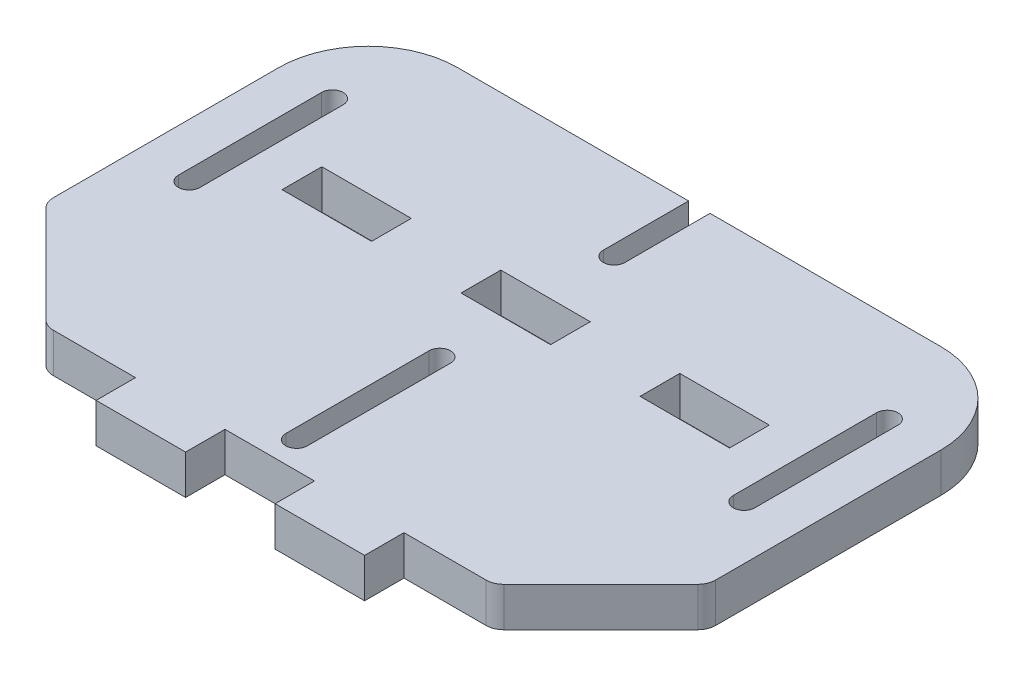
SolidWorks part; units mm, degrees
ref_plane "Front Plane" through (0, 0, 0) normal (0, 0, 1) x (1, 0, 0)
ref_plane "Top Plane" through (0, 0, 0) normal (0, 1, 0) x (1, 0, 0)
ref_plane "Right Plane" through (0, 0, 0) normal (1, 0, 0) x (0, 0, -1)
sketch "Sketch1" plane through (0, 0, 0) normal (0, 1, 0) x (1, 0, 0)
  line L8 (0, -7.5) -> (125, -7.5)
  line L12 (0, -7.5) -> (0, 3.5)
  line L14 (125, -7.5) -> (125, 3.5)
  line L17 (155, 33.5) -> (155, 123.5)
  line L18 (-30, 33.5) -> (-30, 123.5)
  line L23 (140, 58.5) -> (140, 98.5) construction
  line L24 (137, 58.5) -> (137, 98.5)
  line L25 (143, 58.5) -> (143, 98.5)
  line L26 (-15, 58.5) -> (-15, 98.5) construction
  line L27 (-18, 58.5) -> (-18, 98.5)
  line L28 (-12, 58.5) -> (-12, 98.5)
  line L29 (62.5, 11) -> (62.5, 51) construction
  line L30 (59.5, 11) -> (59.5, 51)
  line L31 (65.5, 11) -> (65.5, 51)
  line L32 (59.5, 123.5) -> (-30, 123.5)
  line L33 (65.5, 123.5) -> (65.5, 99.7057)
  line L34 (59.5, 123.5) -> (59.5, 99.7057)
  line L35 (155, 123.5) -> (65.5, 123.5)
  line L36 (125, 3.5) -> (155, 33.5)
  line L37 (0, 3.5) -> (-30, 33.5)
  arc A0 (137, 58.5) -> (143, 58.5) centre (140, 58.5) ccw
  arc A1 (143, 98.5) -> (137, 98.5) centre (140, 98.5) ccw
  arc A2 (-18, 58.5) -> (-12, 58.5) centre (-15, 58.5) ccw
  arc A3 (-12, 98.5) -> (-18, 98.5) centre (-15, 98.5) ccw
  arc A4 (59.5, 11) -> (65.5, 11) centre (62.5, 11) ccw
  arc A5 (65.5, 51) -> (59.5, 51) centre (62.5, 51) ccw
  arc A7 (59.5, 99.7057) -> (65.5, 99.7057) centre (62.5, 99.7057) ccw
  point P4 (-30, 78.5)
  point P18 (140, 78.5)
  point P23 (-15, 78.5)
  point P30 (62.5, 31)
  dimension "D7" = 15
  dimension "D8" = 45
  dimension "D9" = 3
  dimension "D10" = 40
  dimension "D13" = 15
  dimension "D1" = 89.5
  dimension "D12" = 3
  dimension "D2" = 135
  dimension "D3" = 11
  dimension "D4" = 135
  dimension "D5" = 125
  dimension "D6" = 90
extrude "Boss-Extrude6" add sketch "Sketch1" along normal blind 11
sketch "Sketch4" plane through (0, 11, 0) normal (0, 1, 0) x (1, 0, 0)
  line L0 (0, -7.5) -> (125, -7.5) construction
  line L1 (0, -7.5) -> (25, -7.5)
  line L2 (0, -7.5) -> (0, 3.5)
  line L3 (0, 3.5) -> (25, 3.5)
  line L4 (25, -7.5) -> (25, 3.5)
  line L5 (50, -7.5) -> (75, -7.5)
  line L6 (50, -7.5) -> (50, 3.5)
  line L7 (50, 3.5) -> (75, 3.5)
  line L8 (75, -7.5) -> (75, 3.5)
  line L9 (0, 69.45) -> (25, 69.45)
  line L10 (125, -7.5) -> (100, -7.5)
  line L11 (125, -7.5) -> (125, 3.5)
  line L12 (125, 3.5) -> (100, 3.5)
  line L13 (100, -7.5) -> (100, 3.5)
  line L14 (0, 69.45) -> (0, 80.55)
  line L15 (0, 80.55) -> (25, 80.55)
  line L16 (25, 69.45) -> (25, 80.55)
  line L17 (50, 69.45) -> (75, 69.45)
  line L18 (50, 69.45) -> (50, 80.55)
  line L19 (50, 80.55) -> (75, 80.55)
  line L20 (75, 69.45) -> (75, 80.55)
  line L21 (125, 69.45) -> (100, 69.45)
  line L22 (125, 69.45) -> (125, 80.55)
  line L23 (125, 80.55) -> (100, 80.55)
  line L24 (100, 69.45) -> (100, 80.55)
  point P30 (125, 75)
  dimension "D1" = 25
  dimension "D2" = 25
  dimension "D3" = 25
  dimension "D4" = 25
  dimension "D5" = 82.5
  dimension "D6" = 11.1
extrude "Cut-Extrude1" cut sketch "Sketch4" against normal through all
fillet "Fillet1" radius 25 2 edges at (155, 5.5, -123.5) (-30, 5.5, -123.5)
fillet "Fillet2" radius 5 4 edges at (155, 5.5, -33.5) (125, 5.5, -3.5) (0, 5.5, -3.5) (-30, 5.5, -33.5)
